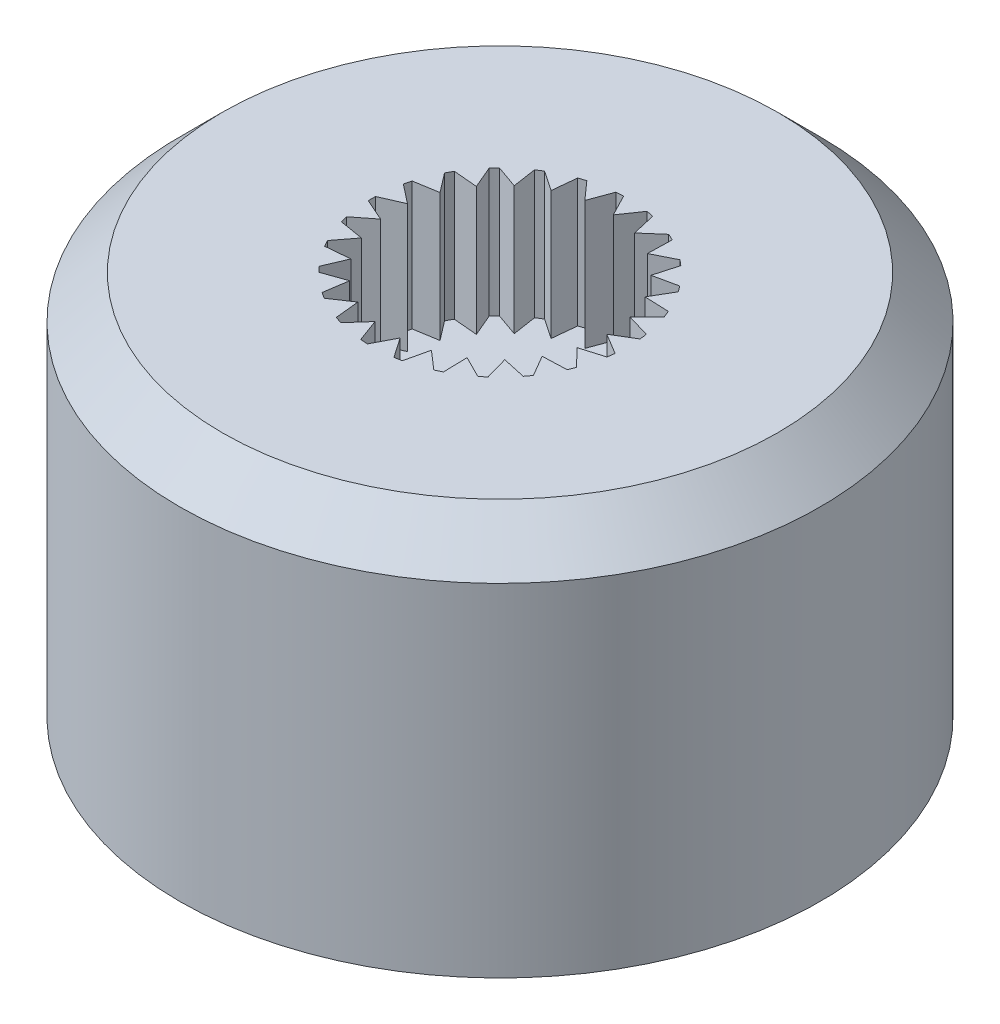
SolidWorks part; units mm, degrees
note: '?' marks a value the reader was unsure of.
ref_plane "Front Plane" through (0, 0, 0) normal (0, 0, 1) x (1, 0, 0)
ref_plane "Top Plane" through (0, 0, 0) normal (0, 1, 0) x (1, 0, 0)
ref_plane "Right Plane" through (0, 0, 0) normal (1, 0, 0) x (0, 0, -1)
ref_axis "X" through (-88.99, 0, 0) along (1, 0, 0)?
ref_axis "Y" through (0, 55, 0) along (0, -1, 0)?
ref_axis "Z" through (0, 0, -88.99) along (0, 0, 1)?
sketch "Sketch1" plane through (0, 0, 0) normal (0, 1, 0) x (1, 0, 0)
  circle A0 centre (0, 0) radius 7.5
  dimension "D1" = 15
extrude "Boss-Extrude1" add sketch "Sketch1" along normal blind 6
hole_wizard "M10x1.0 Tapped Hole1" positions "3DSketch2" profile "Sketch4" tap size "M10x1.0" standard "ANSI Metric"
sketch3d "3DSketch2"
  point P3 (0, 0, 0)
sketch "Sketch4" plane through (0, 0, 0) normal (1, 0, 0) x (0, 0, -1)
  line L0 (0, 0) -> (0, 5)
  line L1 (0, 5) -> (4.5, 5)
  line L2 (4.5, 5) -> (4.5, 0)
  line L5 (4.5, 0) -> (0, 0)
  line L10 (0, 5) -> (-4.5, 5) construction
  line L11 (0, -6.35) -> (0, 107.95) construction
  dimension "Tap Drill Dia." = 9
  dimension "Tap Drill Depth" = 5
  dimension "Drill Angle" = 180
cosmetic thread "Hole Thread1" parameters "D1"=3, "D2"=10
thread "Thread1" pitch 1 start angle 0, offset 1, length 0, pitch 1, diameter 9
ref_plane "Plane1" through (4.5, -1, 0) normal (0, 0, 1) x (1, 0, 0)
sketch "Thread Profile1" plane through (4.5, -1, 0) normal (0, 0, 1) x (1, 0, 0)
  line L0 (0, 0) -> (0, 1) construction
  line L1 (0, 0) -> (0.5413, 0.3125)
  line L2 (0.5413, 0.3125) -> (0.5413, 0.4375)
  line L3 (0.5413, 0.4375) -> (0, 0.75)
  line L4 (0.5413, 0.375) -> (0, 0.375) construction
  line L11 (0, 0) -> (0, 0.75)
  point P2 (0, 0)
  dimension "Pitch" = 1
  dimension "Profile_Angle" = 60
  dimension "Profile_Land" = 0.125
  dimension "Profile_Height" = 0.5413
sketch "Sketch6" plane through (0, 6, 0) normal (0, 1, 0) x (1, 0, 0)
  circle A0 centre (0, 0) radius 3
  circle A1 centre (0, 0) radius 7.5 construction
  circle A2 centre (0, 0) radius 7.5
  dimension "D1" = 6
extrude "Boss-Extrude2" add sketch "Sketch6" along normal blind 3
sketch "Sketch7" plane through (0, 9, 0) normal (0, 1, 0) x (1, 0, 0)
  line L0 (0, 0) -> (3, 0) construction
  line L2 (3, 0.3) -> (3, -0.3)
  line L3 (3, -0.3) -> (2.5, 0)
  line L4 (3, 0.3) -> (2.5, 0)
  circle A0 centre (0, 0) radius 3 construction
  point P7 (2.5703, 0)
  point P9 (2.6, 0.151)
  point P10 (2.5672, -0.0187)
  dimension "D1" = 0.5
  dimension "D2" = 0.6
extrude "Boss-Extrude3" add sketch "Sketch7" against normal up to surface (3 mm away) up to face at (0, 6, 3)
pattern_circular "CirPattern1" count 25 over 360 about axis through (0, 0, 0) along (0, 1, 0) of "Boss-Extrude3"
chamfer "Chamfer1" distance 1 angle 45 1 edges at (0, 9, 7.5)
